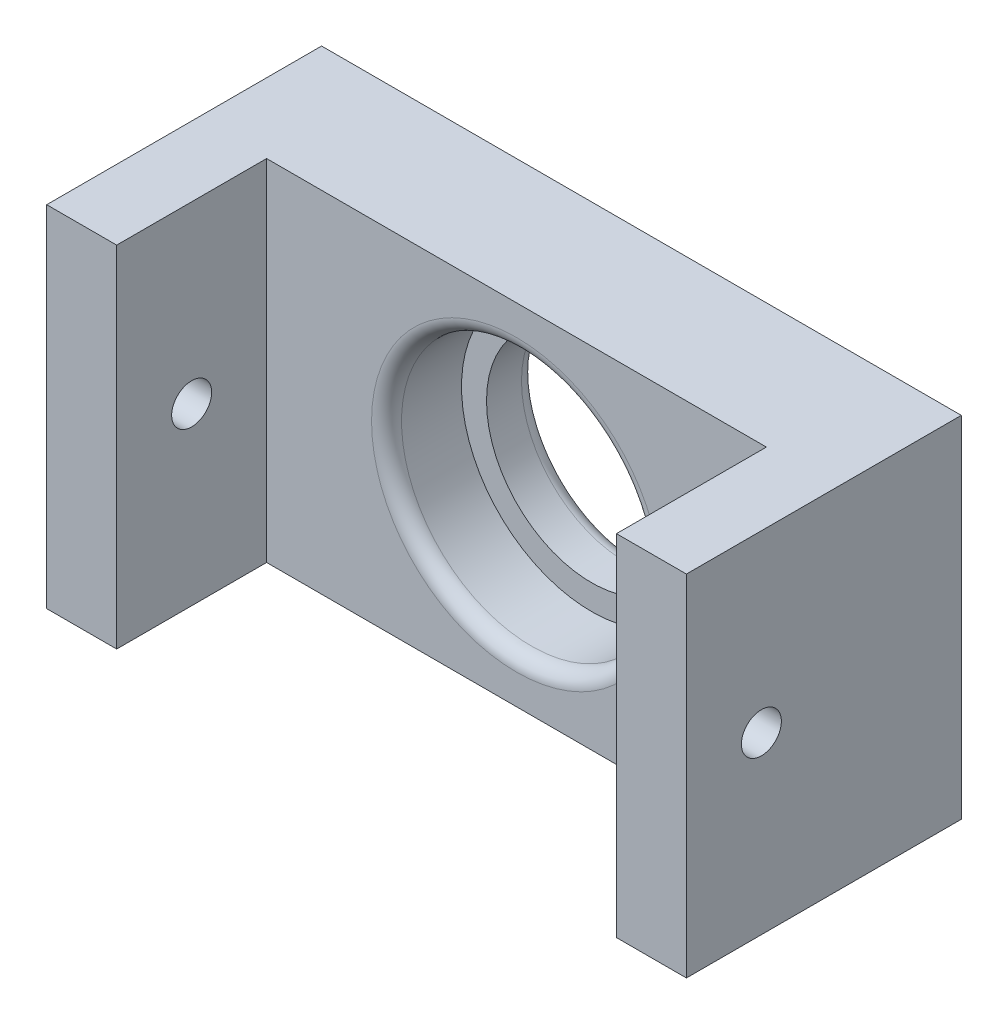
SolidWorks part; units mm, degrees
ref_plane "Front Plane" through (0, 0, 0) normal (0, 0, 1) x (1, 0, 0)
ref_plane "Top Plane" through (0, 0, 0) normal (0, 1, 0) x (1, 0, 0)
ref_plane "Right Plane" through (0, 0, 0) normal (1, 0, 0) x (0, 0, -1)
sketch "Szkic2" plane through (0, 0, 0) normal (0, 0, 1) x (1, 0, 0)
  line L0 (0, 10.5) -> (-32, 10.5)
  line L1 (-32, 10.5) -> (-32, -10.5)
  line L2 (-32, -10.5) -> (0, -10.5)
  line L3 (0, -10.5) -> (32, -10.5)
  line L4 (0, 10.5) -> (32, 10.5)
  line L5 (32, 10.5) -> (32, -10.5)
  line L7 (-32, 10.5) -> (32, 10.5)
  line L8 (-32, 10.5) -> (-32, 17.5)
  line L9 (-32, 17.5) -> (32, 17.5)
  line L10 (32, 10.5) -> (32, 17.5)
  line L11 (-32, -10.5) -> (32, -10.5)
  line L12 (-32, -10.5) -> (-32, -17.5)
  line L13 (-32, -17.5) -> (32, -17.5)
  line L14 (32, -10.5) -> (32, -17.5)
  circle A0 centre (0, 0) radius 10.5
  point P13 (0, 0)
  point P14 (0, 0)
  dimension "D1" = 21
  dimension "D2" = 32
  dimension "D3" = 32
  dimension "D4" = 7
  dimension "D5" = 7
extrude "Dodanie-wyciągnięcie1" add sketch "Szkic2" along normal blind 12.5 contours A0 L0 L1 L2 | A0 L3 L5 L4 | L4 L10 L9 L8 L0 | L14 L3 L2 L12 L13 region at (-20.0077, 0, 0) region at (0, 14, 0) region at (20.0077, 0, 0) region at (0, -14, 0)
sketch "Szkic3" plane through (0, 0, 12.5) normal (0, 0, 1) x (1, 0, 0)
  circle A0 centre (0, 0) radius 13
  dimension "D1" = 26
extrude "Wytnij-wyciągnięcie1" cut sketch "Szkic3" against normal blind 7.5
sketch "Szkic4" plane through (0, 0, 12.5) normal (0, 0, 1) x (1, 0, 0)
  line L0 (-32, -17.5) -> (32, -17.5) construction
  line L1 (-32, 17.5) -> (-25, 17.5)
  line L2 (-32, 17.5) -> (-32, -17.5)
  line L3 (-32, -17.5) -> (-25, -17.5)
  line L4 (-25, 17.5) -> (-25, -17.5)
  line L6 (32, 17.5) -> (25, 17.5)
  line L7 (32, 17.5) -> (32, -17.5)
  line L8 (32, -17.5) -> (25, -17.5)
  line L9 (25, 17.5) -> (25, -17.5)
  dimension "D1" = 7
  dimension "D2" = 7
extrude "Dodanie-wyciągnięcie2" add sketch "Szkic4" along normal blind 15
sketch "Szkic6" plane through (25, 0, 0) normal (-1, 0, 0) x (0, 0, 1)
  circle A0 centre (20, 0) radius 2
  dimension "D1" = 4
extrude "Wytnij-wyciągnięcie2" cut sketch "Szkic6" against normal blind 7 contours A0
sketch "Szkic7" plane through (-25, 0, 0) normal (1, 0, 0) x (0, 0, -1)
  circle A0 centre (-20, 0) radius 2
  dimension "D1" = 4
extrude "Wytnij-wyciągnięcie3" cut sketch "Szkic7" against normal blind 7 contours A0
fillet "Zaokrąglenie2" radius 1.5 1 edges at (13, 0, 12.5)
fillet "Zaokrąglenie3" radius 1.5 1 edges at (10.5, 0, 0)
